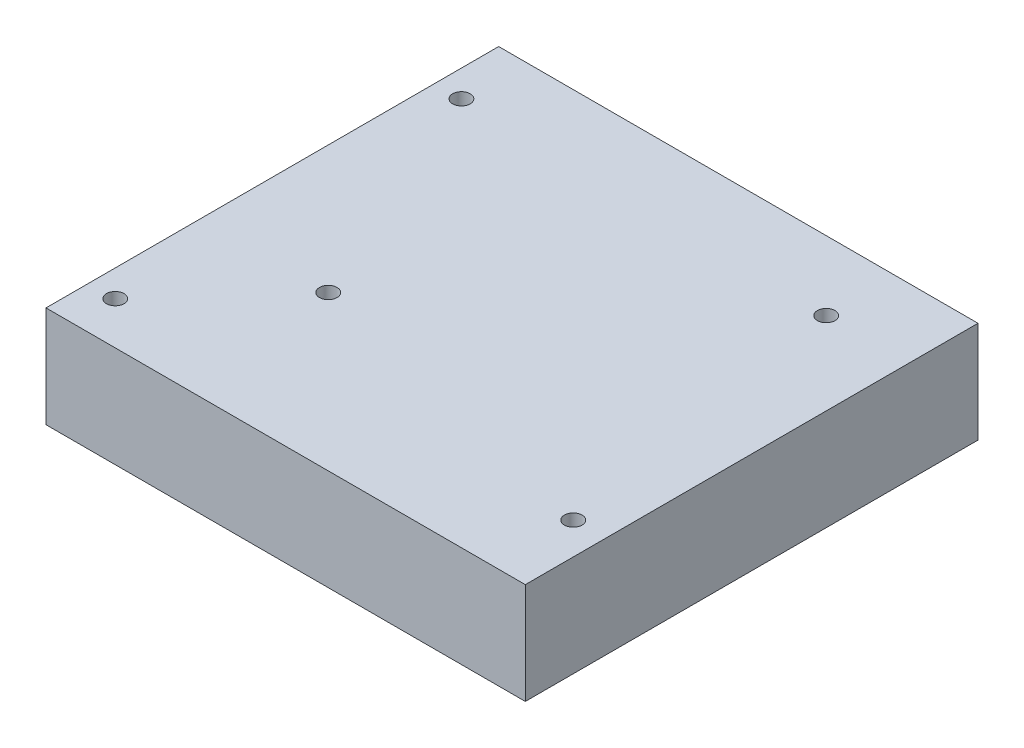
SolidWorks part; units mm, degrees
ref_plane "Front Plane" through (0, 0, 0) normal (0, 0, 1) x (1, 0, 0)
ref_plane "Top Plane" through (0, 0, 0) normal (0, 1, 0) x (1, 0, 0)
ref_plane "Right Plane" through (0, 0, 0) normal (1, 0, 0) x (0, 0, -1)
sketch "Sketch1" plane through (0, 0, 0) normal (0, 1, 0) x (1, 0, 0)
  line L1 (0, 0) -> (90, 0)
  line L2 (0, 0) -> (0, 85)
  line L3 (0, 85) -> (90, 85)
  line L4 (90, 0) -> (90, 85)
  circle A0 centre (5, 73) radius 1.65
  circle A1 centre (5, 8) radius 1.65
  circle A2 centre (84, 15) radius 1.65
  circle A3 centre (24, 29) radius 1.65
  circle A4 centre (74.5, 72) radius 1.65
  point P7 (5, 8)
  point P8 (24, 29)
  point P9 (84, 15)
  point P10 (74.5, 72)
  point P23 (90, 5.1159)
  point P24 (90, 5.7086)
  dimension "D13" = 3.3
  dimension "D14" = 3.3
  dimension "D15" = 3.3
  dimension "D16" = 3.3
  dimension "D17" = 3.3
  dimension "D1" = 90
  dimension "D2" = 85
  dimension "D3" = 5
  dimension "D4" = 8
  dimension "D5" = 5
  dimension "D6" = 12
  dimension "D7" = 24
  dimension "D8" = 29
  dimension "D9" = 15.5
  dimension "D10" = 13
  dimension "D11" = 6
  dimension "D12" = 15
extrude "Boss-Extrude1" add sketch "Sketch1" along normal blind 19
sketch "Sketch2" plane through (0, 19, 0) normal (0, 1, 0) x (1, 0, 0)
  line L0 (0, 42.5) -> (90, 42.5) construction
  line L1 (0, 85) -> (0, 0) construction
  line L2 (90, 0) -> (90, 85) construction
  point P6 (45, 42.5)
sketch "Sketch4" plane through (0, 0, 0) normal (0, -1, 0) x (1, 0, 0)
  line L0 (0, -85) -> (0, 0) construction
  line L1 (0, 0) -> (90, 0) construction
  circle A0 centre (30, -4) radius 10
  circle A1 centre (13, -30) radius 10
  dimension "D5" = 20
  dimension "D6" = 20
  dimension "D1" = 13
  dimension "D2" = 30
  dimension "D3" = 4
  dimension "D4" = 30
equation "\"rad\"=0.33"
equation "\"D13@Sketch1\"=\"rad\""
equation "\"D14@Sketch1\"=\"rad\""
equation "\"D15@Sketch1\"=\"rad\""
equation "\"D16@Sketch1\"=\"rad\""
equation "\"D17@Sketch1\"=\"rad\""
